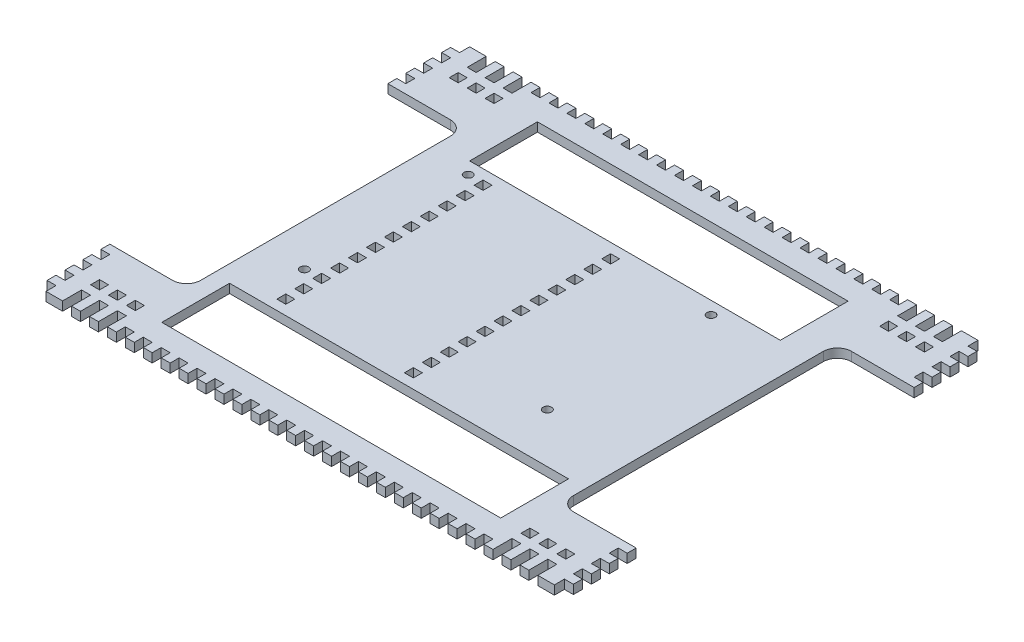
SolidWorks part; units mm, degrees
ref_plane "Front Plane" through (0, 0, 0) normal (0, 0, 1) x (1, 0, 0)
ref_plane "Top Plane" through (0, 0, 0) normal (0, 1, 0) x (1, 0, 0)
ref_plane "Right Plane" through (0, 0, 0) normal (1, 0, 0) x (0, 0, -1)
sketch "Sketch1" plane through (0, 0, 0) normal (0, 1, 0) x (1, 0, 0)
  line L1 (90, -75) -> (-90, -75)
  line L2 (90, -75) -> (90, 75)
  line L3 (90, 75) -> (-90, 75)
  line L4 (-90, -75) -> (-90, 75)
  line L5 (90, -75) -> (-90, 75) construction
  line L6 (90, 75) -> (-90, -75) construction
  point P0 (0, 0)
  dimension "D1" = 180
  dimension "D2" = 150
extrude "Boss-Extrude1" add sketch "Sketch1" along normal blind 3.175
sketch "Sketch2" plane through (0, 3.175, 0) normal (0, 1, 0) x (1, 0, 0)
  line L1 (45, -39.5) -> (-55, -39.5) construction
  line L2 (45, -39.5) -> (45, 39.5) construction
  line L3 (45, 39.5) -> (-55, 39.5) construction
  line L4 (-55, -39.5) -> (-55, 39.5) construction
  line L5 (45, -39.5) -> (-55, 39.5) construction
  line L6 (45, 39.5) -> (-55, -39.5) construction
  point P0 (-5, 0)
  dimension "D1" = 79
  dimension "D2" = 100
  dimension "D3" = 5
sketch "Sketch3" plane through (0, 3.175, 0) normal (0, 1, 0) x (1, 0, 0)
  line L0 (45, 39.5) -> (-55, 39.5) construction
  line L1 (-55, -39.5) -> (-55, 39.5) construction
  line L2 (45, -39.5) -> (45, 39.5) construction
  line L3 (45, -39.5) -> (-55, -39.5) construction
  circle A0 centre (-51, 35.5) radius 1.375
  circle A1 centre (-51, -22.5) radius 1.375
  circle A2 centre (35, 35.5) radius 1.375
  circle A3 centre (35, -22.5) radius 1.375
  dimension "D1" = 2.75
  dimension "D2" = 4
  dimension "D3" = 4
  dimension "D4" = 4
  dimension "D5" = 10
  dimension "D6" = 10
  dimension "D7" = 17
  dimension "D8" = 17
  dimension "D9" = 4
extrude "Cut-Extrude1" cut sketch "Sketch3" against normal blind 10
sketch "Sketch4" plane through (0, 3.175, 0) normal (0, 1, 0) x (1, 0, 0)
  line L0 (-90, 75) -> (-90, -75) construction
  line L1 (-86.825, -1.5875) -> (-93.175, -1.5875)
  line L2 (-86.825, -1.5875) -> (-86.825, 1.5875)
  line L3 (-86.825, 1.5875) -> (-93.175, 1.5875)
  line L4 (-93.175, -1.5875) -> (-93.175, 1.5875)
  line L5 (-86.825, -1.5875) -> (-93.175, 1.5875) construction
  line L6 (-86.825, 1.5875) -> (-93.175, -1.5875) construction
  point P0 (-90, 0)
  dimension "D1" = 6.35
  dimension "D2" = 3.175
extrude "Boss-Extrude2" add sketch "Sketch4" against normal up to surface (3.175 mm away) up to face at (-51, 0, 23.875)
pattern_linear "LPattern1" count 12 spacing 6.35 along (0, 0, 1) count 12 spacing 6.35 along (0, 0, -1) of "Boss-Extrude2"
mirror "Mirror1" about plane through (0, 0, 0) normal (1, 0, 0) of "LPattern1", "Boss-Extrude2"
sketch "Sketch8" plane through (0, 3.175, 0) normal (0, 1, 0) x (1, 0, 0)
  line L0 (-93.175, -73.4125) -> (93.175, -73.4125) construction
  line L3 (-90, -75) -> (90, -75) construction
  dimension "D1" = 1.5875
sketch "Sketch6" plane through (0, 3.175, 0) normal (0, 1, 0) x (1, 0, 0)
  line L0 (-93.175, -73.4125) -> (93.175, -73.4125) construction
  line L1 (-1.5875, -71.825) -> (1.5875, -71.825)
  line L2 (-1.5875, -71.825) -> (-1.5875, -75)
  line L3 (-1.5875, -75) -> (1.5875, -75)
  line L4 (1.5875, -71.825) -> (1.5875, -75)
  line L5 (-1.5875, -71.825) -> (1.5875, -75) construction
  line L6 (-1.5875, -75) -> (1.5875, -71.825) construction
  point P0 (0, -73.4125)
  dimension "D1" = 3.175
  dimension "D2" = 3.175
extrude "Cut-Extrude3" cut sketch "Sketch6" against normal blind 10
pattern_linear "LPattern2" count 14 spacing 6.35 along (1, 0, 0) count 14 spacing 6.35 along (-1, 0, 0) of "Cut-Extrude3"
mirror "Mirror2" about plane through (0, 0, 0) normal (0, 0, 1) of "LPattern2", "Cut-Extrude3"
sketch "Sketch11" plane through (0, 3.175, 0) normal (0, 1, 0) x (1, 0, 0)
  line L1 (-60, 45) -> (-50, 45)
  line L2 (-60, 45) -> (-60, 48.175)
  line L3 (-60, 48.175) -> (-50, 48.175)
  line L4 (-50, 45) -> (-50, 48.175)
  point P4 (-50, 46.5875)
  dimension "D1" = 10
  dimension "D2" = 3.175
  dimension "D3" = 50
  dimension "D4" = 45
extrude "Cut-Extrude6" [suppressed] cut sketch "Sketch11" against normal up to next
mirror "Mirror3" [suppressed] about plane through (0, 0, 0) normal (0, 0, 1)
sketch "Sketch12" plane through (0, 3.175, 0) normal (0, 1, 0) x (1, 0, 0)
  line L0 (0, 64) -> (0, 40)
  line L1 (0, 40) -> (55, 40)
  line L3 (0, 64) -> (55, 64)
  line L4 (55, 40) -> (55, 64)
  line L5 (0, -40) -> (60, -40)
  line L7 (0, -64) -> (60, -64)
  line L8 (60, -40) -> (60, -64)
  line L9 (0, -64) -> (0, -40)
  dimension "D1" = 24
  dimension "D2" = 24
  dimension "D3" = 40
  dimension "D4" = 40
  dimension "D5" = 55
  dimension "D6" = 60
extrude "Cut-Extrude7" cut sketch "Sketch12" against normal blind 10
sketch "Sketch13" plane through (0, 3.175, 0) normal (0, 1, 0) x (1, 0, 0)
  line L7 (-1.5875, 4.7625) -> (1.5875, 4.7625)
  line L8 (-1.5875, 4.7625) -> (-1.5875, 1.5875)
  line L9 (-1.5875, 1.5875) -> (1.5875, 1.5875)
  line L10 (1.5875, 4.7625) -> (1.5875, 1.5875)
  line L11 (-1.5875, 4.7625) -> (1.5875, 1.5875) construction
  line L12 (-1.5875, 1.5875) -> (1.5875, 4.7625) construction
  point P9 (0, 3.175)
  dimension "D1" = 3.175
  dimension "D4" = 3.175
  dimension "D5" = 3.175
extrude "Cut-Extrude8" cut sketch "Sketch13" against normal blind 10
pattern_linear "LPattern3" count 7 spacing 6.35 along (0, 0, 1) count 7 spacing 6.35 along (0, 0, -1) skipping (0, 6) of "Cut-Extrude8"
sketch "Sketch15" plane through (0, 3.175, 0) normal (0, 1, 0) x (1, 0, 0)
  circle A0 centre (-51, 35.5) radius 1.5
  circle A1 centre (35, 35.5) radius 1.5
  circle A2 centre (35, -22.5) radius 1.5
  circle A3 centre (-51, -22.5) radius 1.5
  dimension "D1" = 3
extrude "Cut-Extrude10" cut sketch "Sketch15" against normal blind 10
sketch "Sketch16" plane through (0, 3.175, 0) normal (0, 1, 0) x (1, 0, 0)
  line L0 (58.35, 31.5) -> (50.35, 31.5) construction
  line L1 (54.35, -31.5) -> (-64.35, -31.5) construction
  line L2 (54.35, -31.5) -> (54.35, 31.5) construction
  line L3 (54.35, 31.5) -> (-64.35, 31.5) construction
  line L4 (-64.35, -31.5) -> (-64.35, 31.5) construction
  line L5 (54.35, -31.5) -> (-64.35, 31.5) construction
  line L6 (54.35, 31.5) -> (-64.35, -31.5) construction
  line L7 (58.35, 30) -> (50.35, 30)
  line L8 (58.35, 33) -> (50.35, 33)
  line L9 (50.35, -31.5) -> (58.35, -31.5) construction
  line L10 (50.35, -30) -> (58.35, -30)
  line L11 (50.35, -33) -> (58.35, -33)
  line L12 (-60.35, 31.5) -> (-68.35, 31.5) construction
  line L13 (-60.35, 30) -> (-68.35, 30)
  line L14 (-60.35, 33) -> (-68.35, 33)
  line L15 (-60.35, -31.5) -> (-68.35, -31.5) construction
  line L16 (-60.35, -33) -> (-68.35, -33)
  line L17 (-60.35, -30) -> (-68.35, -30)
  arc A0 (58.35, 30) -> (58.35, 33) centre (58.35, 31.5) ccw
  arc A1 (50.35, 33) -> (50.35, 30) centre (50.35, 31.5) ccw
  arc A2 (50.35, -30) -> (50.35, -33) centre (50.35, -31.5) ccw
  arc A3 (58.35, -33) -> (58.35, -30) centre (58.35, -31.5) ccw
  arc A4 (-60.35, 30) -> (-60.35, 33) centre (-60.35, 31.5) ccw
  arc A5 (-68.35, 33) -> (-68.35, 30) centre (-68.35, 31.5) ccw
  arc A6 (-60.35, -33) -> (-60.35, -30) centre (-60.35, -31.5) ccw
  arc A7 (-68.35, -30) -> (-68.35, -33) centre (-68.35, -31.5) ccw
  point P0 (-5, 0)
  point P8 (54.35, 31.5)
  point P15 (54.35, -31.5)
  point P21 (-64.35, 31.5)
  point P28 (-64.35, -31.5)
  dimension "D1" = 118.7
  dimension "D2" = 63
  dimension "D3" = 3
  dimension "D4" = 8
  dimension "D5" = 3
  dimension "D6" = 8
  dimension "D7" = 3
  dimension "D8" = 8
  dimension "D9" = 8
  dimension "D10" = 3
extrude "Cut-Extrude11" [suppressed] cut sketch "Sketch16" against normal blind 10
sketch "Sketch17" plane through (0, 3.175, 0) normal (0, 1, 0) x (1, 0, 0)
  line L1 (-71.4375, 71.825) -> (-68.2625, 71.825)
  line L2 (-71.4375, 71.825) -> (-71.4375, 68.65)
  line L3 (-71.4375, 68.65) -> (-68.2625, 68.65)
  line L4 (-68.2625, 71.825) -> (-68.2625, 68.65)
  line L5 (-77.7875, 71.825) -> (-74.6125, 71.825)
  line L6 (-77.7875, 71.825) -> (-77.7875, 68.65)
  line L7 (-77.7875, 68.65) -> (-74.6125, 68.65)
  line L8 (-74.6125, 71.825) -> (-74.6125, 68.65)
  line L9 (-84.1375, 71.825) -> (-80.9625, 71.825)
  line L10 (-84.1375, 71.825) -> (-84.1375, 68.65)
  line L11 (-84.1375, 68.65) -> (-80.9625, 68.65)
  line L12 (-80.9625, 71.825) -> (-80.9625, 68.65)
  dimension "D1" = 3.175
extrude "Cut-Extrude12" cut sketch "Sketch17" against normal blind 10
mirror "Mirror4" about plane through (0, 0, 0) normal (0, 0, 1) of "Cut-Extrude12"
mirror "Mirror5" about plane through (0, 0, 0) normal (1, 0, 0) of "Mirror4", "Cut-Extrude12"
mirror "Mirror6" about plane through (0, 0, 0) normal (1, 0, 0) of "Cut-Extrude7"
sketch "Sketch18" plane through (0, 3.175, 0) normal (0, 1, 0) x (1, 0, 0)
  line L5 (-1.5875, 11.1125) -> (-1.5875, 7.9375) construction
  line L10 (-43.5875, 4.7625) -> (-46.7625, 4.7625)
  line L11 (-43.5875, 4.7625) -> (-43.5875, 1.5875)
  line L12 (-43.5875, 1.5875) -> (-46.7625, 1.5875)
  line L13 (-46.7625, 4.7625) -> (-46.7625, 1.5875)
  dimension "D4" = 3.175
  dimension "D5" = 3.175
  dimension "D6" = 42
extrude "Cut-Extrude13" cut sketch "Sketch18" against normal blind 10
pattern_linear "LPattern4" count 7 spacing 6.35 along (0, 0, 1) count 7 spacing 6.35 along (0, 0, -1) skipping (0, 6) of "Cut-Extrude13"
sketch "Sketch20" plane through (0, 3.175, 0) normal (0, 1, 0) x (1, 0, 0)
  line L0 (-4.7625, 71.825) -> (-4.7625, 64)
  line L1 (-4.7625, 75) -> (4.7625, 75)
  line L2 (-4.7625, 75) -> (-4.7625, 71.825)
  line L4 (4.7625, 75) -> (4.7625, 71.825)
  line L5 (55, 64) -> (-55, 64) construction
  line L6 (-4.7625, 64) -> (4.7625, 64)
  line L7 (4.7625, 71.825) -> (4.7625, 64)
extrude "Cut-Extrude14" [suppressed] cut sketch "Sketch20" against normal blind 10
sketch "Sketch21" plane through (0, 3.175, 0) normal (0, 1, 0) x (1, 0, 0)
  line L0 (100, 49.2125) -> (66, 49.2125)
  line L4 (100, 49.2125) -> (100, -49.2125)
  line L10 (66, 49.2125) -> (66, -49.2125)
  line L11 (90, 14.2875) -> (90, 17.4625) construction
  line L14 (100, -49.2125) -> (66, -49.2125)
  dimension "D4" = 24
extrude "Cut-Extrude15" cut sketch "Sketch21" against normal blind 10
sketch "Sketch22" plane through (0, 3.175, 0) normal (0, 1, 0) x (1, 0, 0)
  line L1 (-84.1375, 65.0875) -> (-80.9625, 65.0875)
  line L2 (-84.1375, 65.0875) -> (-84.1375, 61.9125)
  line L3 (-84.1375, 61.9125) -> (-80.9625, 61.9125)
  line L4 (-80.9625, 65.0875) -> (-80.9625, 61.9125)
  line L5 (-77.7875, 65.0875) -> (-74.6125, 65.0875)
  line L6 (-77.7875, 65.0875) -> (-77.7875, 61.9125)
  line L7 (-77.7875, 61.9125) -> (-74.6125, 61.9125)
  line L8 (-74.6125, 65.0875) -> (-74.6125, 61.9125)
  line L9 (-71.4375, 65.0875) -> (-68.2625, 65.0875)
  line L10 (-71.4375, 65.0875) -> (-71.4375, 61.9125)
  line L11 (-71.4375, 61.9125) -> (-68.2625, 61.9125)
  line L12 (-68.2625, 65.0875) -> (-68.2625, 61.9125)
extrude "Cut-Extrude16" cut sketch "Sketch22" against normal blind 10
mirror "Mirror7" about plane through (0, 0, 0) normal (1, 0, 0) of "Cut-Extrude16"
mirror "Mirror8" about plane through (0, 0, 0) normal (0, 0, 1) of "Mirror7", "Cut-Extrude16"
mirror "Mirror9" about plane through (0, 0, 0) normal (1, 0, 0) of "Cut-Extrude15"
fillet "Fillet1" radius 5 4 edges at (66, 1.5875, 49.2125) (66, 1.5875, -49.2125) (-66, 1.5875, 49.2125) (-66, 1.5875, -49.2125)
sketch "Sketch24" plane through (0, 3.175, 0) normal (0, 1, 0) x (1, 0, 0)
  line L1 (-84.1375, 68.65) -> (-80.9625, 68.65)
  line L2 (-84.1375, 68.65) -> (-84.1375, 68.2625)
  line L3 (-84.1375, 68.2625) -> (-80.9625, 68.2625)
  line L4 (-80.9625, 68.65) -> (-80.9625, 68.2625)
  line L5 (-77.7875, 68.65) -> (-74.6125, 68.65)
  line L6 (-77.7875, 68.65) -> (-77.7875, 68.2625)
  line L7 (-77.7875, 68.2625) -> (-74.6125, 68.2625)
  line L8 (-74.6125, 68.65) -> (-74.6125, 68.2625)
  line L9 (-71.4375, 68.65) -> (-68.2625, 68.65)
  line L10 (-71.4375, 68.65) -> (-71.4375, 68.2625)
  line L11 (-71.4375, 68.2625) -> (-68.2625, 68.2625)
  line L12 (-68.2625, 68.65) -> (-68.2625, 68.2625)
extrude "Cut-Extrude17" cut sketch "Sketch24" against normal blind 10
mirror "Mirror10" about plane through (0, 0, 0) normal (1, 0, 0) of "Cut-Extrude17" second plane through (0, 0, 0) second plane normal (0, 0, 1)
